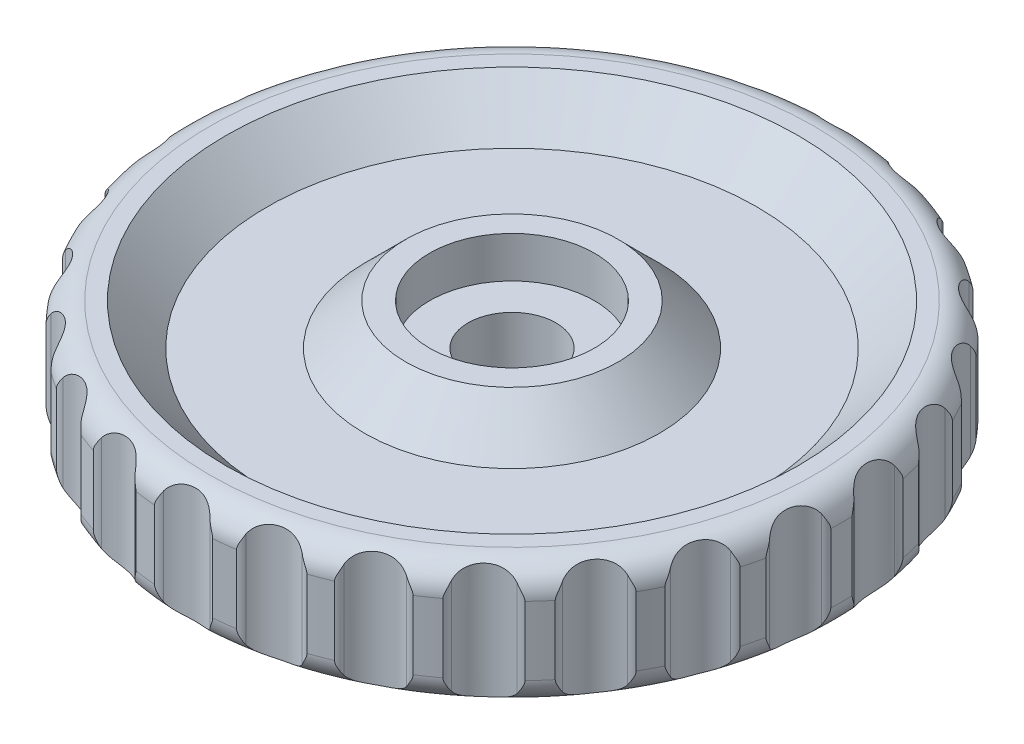
SolidWorks part; units mm, degrees
ref_plane "Front Plane" through (0, 0, 0) normal (0, 0, 1) x (1, 0, 0)
ref_plane "Top Plane" through (0, 0, 0) normal (0, 1, 0) x (1, 0, 0)
ref_plane "Right Plane" through (0, 0, 0) normal (1, 0, 0) x (0, 0, -1)
sketch "Sketch1" plane through (0, 0, 0) normal (0, 1, 0) x (1, 0, 0)
  circle A0 centre (0, 0) radius 1.6
  circle A1 centre (0, 0) radius 12
  dimension "D1" = 24
  dimension "D2" = 3.2
extrude "Boss-Extrude1" add sketch "Sketch1" along normal blind 4.5
fillet "Fillet1" radius 1 2 edges at (0, 0, 12) (0, 4.5, 12)
sketch "Sketch2" plane through (0, 4.5, 0) normal (0, 1, 0) x (1, 0, 0)
  line L0 (0, 14.2529) -> (0, 11.2106) construction
  line L1 (-1.1973, 11.9524) -> (0, 13.275)
  line L2 (0, 13.275) -> (1.1973, 11.9524)
  line L3 (1.6979, 11.8917) -> (3.1769, 12.8893)
  line L4 (3.1769, 12.8893) -> (4.0229, 11.3186)
  line L5 (3.4109, 13.8387) -> (2.6829, 10.8849) construction
  line L6 (4.4944, 11.1398) -> (6.1692, 11.7544)
  line L7 (6.1692, 11.7544) -> (6.6147, 10.0269)
  line L8 (6.6236, 12.6203) -> (5.2098, 9.9265) construction
  line L9 (7.0297, 9.7405) -> (8.803, 9.9365)
  line L10 (8.803, 9.9365) -> (8.8221, 8.1526)
  line L11 (9.4514, 10.6684) -> (7.434, 8.3913) construction
  line L12 (9.1565, 7.7751) -> (10.9251, 7.5411)
  line L13 (10.9251, 7.5411) -> (10.5168, 5.8044)
  line L14 (11.7299, 8.0966) -> (9.2262, 6.3684) construction
  line L15 (10.7512, 5.3579) -> (12.4124, 4.7074)
  line L16 (12.4124, 4.7074) -> (11.6003, 3.1189)
  line L17 (13.3267, 5.0541) -> (10.4821, 3.9753) construction
  line L18 (11.721, 2.6293) -> (13.1782, 1.6001)
  line L19 (13.1782, 1.6001) -> (12.0096, 0.2521)
  line L20 (14.149, 1.718) -> (11.1289, 1.3513) construction
  line L21 (12.0096, -0.2521) -> (13.1782, -1.6001)
  line L22 (13.1782, -1.6001) -> (11.721, -2.6293)
  line L23 (14.149, -1.718) -> (11.1289, -1.3513) construction
  line L24 (11.6003, -3.1189) -> (12.4124, -4.7074)
  line L25 (12.4124, -4.7074) -> (10.7512, -5.3579)
  line L26 (13.3267, -5.0541) -> (10.4821, -3.9753) construction
  line L27 (10.5168, -5.8044) -> (10.9251, -7.5411)
  line L28 (10.9251, -7.5411) -> (9.1565, -7.7751)
  line L29 (11.7299, -8.0966) -> (9.2262, -6.3684) construction
  line L30 (8.8221, -8.1526) -> (8.803, -9.9365)
  line L31 (8.803, -9.9365) -> (7.0297, -9.7405)
  line L32 (9.4514, -10.6684) -> (7.434, -8.3913) construction
  line L33 (6.6147, -10.0269) -> (6.1692, -11.7544)
  line L34 (6.1692, -11.7544) -> (4.4944, -11.1398)
  line L35 (6.6236, -12.6203) -> (5.2098, -9.9265) construction
  line L36 (4.0229, -11.3186) -> (3.1769, -12.8893)
  line L37 (3.1769, -12.8893) -> (1.6979, -11.8917)
  line L38 (3.4109, -13.8387) -> (2.6829, -10.8849) construction
  line L39 (1.1973, -11.9524) -> (0, -13.275)
  line L40 (0, -13.275) -> (-1.1973, -11.9524)
  line L41 (0, -14.2529) -> (0, -11.2106) construction
  line L42 (-1.6979, -11.8917) -> (-3.1769, -12.8893)
  line L43 (-3.1769, -12.8893) -> (-4.0229, -11.3186)
  line L44 (-3.4109, -13.8387) -> (-2.6829, -10.8849) construction
  line L45 (-4.4944, -11.1398) -> (-6.1692, -11.7544)
  line L46 (-6.1692, -11.7544) -> (-6.6147, -10.0269)
  line L47 (-6.6236, -12.6203) -> (-5.2098, -9.9265) construction
  line L48 (-7.0297, -9.7405) -> (-8.803, -9.9365)
  line L49 (-8.803, -9.9365) -> (-8.8221, -8.1526)
  line L50 (-9.4514, -10.6684) -> (-7.434, -8.3913) construction
  line L51 (-9.1565, -7.7751) -> (-10.9251, -7.5411)
  line L52 (-10.9251, -7.5411) -> (-10.5168, -5.8044)
  line L53 (-11.7299, -8.0966) -> (-9.2262, -6.3684) construction
  line L54 (-10.7512, -5.3579) -> (-12.4124, -4.7074)
  line L55 (-12.4124, -4.7074) -> (-11.6003, -3.1189)
  line L56 (-13.3267, -5.0541) -> (-10.4821, -3.9753) construction
  line L57 (-11.721, -2.6293) -> (-13.1782, -1.6001)
  line L58 (-13.1782, -1.6001) -> (-12.0096, -0.2521)
  line L59 (-14.149, -1.718) -> (-11.1289, -1.3513) construction
  line L60 (-12.0096, 0.2521) -> (-13.1782, 1.6001)
  line L61 (-13.1782, 1.6001) -> (-11.721, 2.6293)
  line L62 (-14.149, 1.718) -> (-11.1289, 1.3513) construction
  line L63 (-11.6003, 3.1189) -> (-12.4124, 4.7074)
  line L64 (-12.4124, 4.7074) -> (-10.7512, 5.3579)
  line L65 (-13.3267, 5.0541) -> (-10.4821, 3.9753) construction
  line L66 (-10.5168, 5.8044) -> (-10.9251, 7.5411)
  line L67 (-10.9251, 7.5411) -> (-9.1565, 7.7751)
  line L68 (-11.7299, 8.0966) -> (-9.2262, 6.3684) construction
  line L69 (-8.8221, 8.1526) -> (-8.803, 9.9365)
  line L70 (-8.803, 9.9365) -> (-7.0297, 9.7405)
  line L71 (-9.4514, 10.6684) -> (-7.434, 8.3913) construction
  line L72 (-6.6147, 10.0269) -> (-6.1692, 11.7544)
  line L73 (-6.1692, 11.7544) -> (-4.4944, 11.1398)
  line L74 (-6.6236, 12.6203) -> (-5.2098, 9.9265) construction
  line L75 (-4.0229, 11.3186) -> (-3.1769, 12.8893)
  line L76 (-3.1769, 12.8893) -> (-1.6979, 11.8917)
  line L77 (-3.4109, 13.8387) -> (-2.6829, 10.8849) construction
  arc A0 (-0.847, 11.8378) -> (0.847, 11.8378) centre (0, 12.8028) ccw
  arc A1 (-0.847, 11.8378) -> (-1.1973, 11.9524) centre (-1.1265, 11.5764) ccw
  arc A2 (0.847, 11.8378) -> (1.1973, 11.9524) centre (1.1265, 11.5764) cw
  arc A3 (2.0106, 11.6965) -> (3.6554, 11.2911) centre (3.0639, 12.4308) ccw
  arc A4 (2.0106, 11.6965) -> (1.6979, 11.8917) centre (1.6767, 11.5096) ccw
  arc A5 (3.6554, 11.2911) -> (4.0229, 11.3186) centre (3.8642, 10.9704) cw
  arc A6 (4.7513, 10.8755) -> (6.2513, 10.0882) centre (5.9498, 11.3363) ccw
  arc A7 (4.7513, 10.8755) -> (4.4944, 11.1398) centre (4.3824, 10.7739) ccw
  arc A8 (6.2513, 10.0882) -> (6.6147, 10.0269) centre (6.3773, 9.7269) cw
  arc A9 (7.2159, 9.4224) -> (8.4839, 8.299) centre (8.4898, 9.583) ccw
  arc A10 (7.2159, 9.4224) -> (7.0297, 9.7405) centre (6.8334, 9.412) ccw
  arc A11 (8.4839, 8.299) -> (8.8221, 8.1526) centre (8.5197, 7.9181) cw
  arc A12 (9.2612, 7.4217) -> (10.2235, 6.0276) centre (10.5365, 7.2728) ccw
  arc A13 (9.2612, 7.4217) -> (9.1565, 7.7751) centre (8.8873, 7.5032) ccw
  arc A14 (10.2235, 6.0276) -> (10.5168, 5.8044) centre (10.1671, 5.6491) cw
  arc A15 (10.7682, 4.9897) -> (11.3689, 3.4058) centre (11.9708, 4.5399) ccw
  arc A16 (10.7682, 4.9897) -> (10.7512, 5.3579) centre (10.4247, 5.1583) ccw
  arc A17 (11.3689, 3.4058) -> (11.6003, 3.1189) centre (11.2236, 3.0518) cw
  arc A18 (11.6494, 2.2677) -> (11.8536, 0.5861) centre (12.7094, 1.5432) ccw
  arc A19 (11.6494, 2.2677) -> (11.721, 2.6293) centre (11.3562, 2.5136) ccw
  arc A20 (11.8536, 0.5861) -> (12.0096, 0.2521) centre (11.6278, 0.2771) cw
  arc A21 (11.8536, -0.5861) -> (11.6494, -2.2677) centre (12.7094, -1.5432) ccw
  arc A22 (11.8536, -0.5861) -> (12.0096, -0.2521) centre (11.6278, -0.2771) ccw
  arc A23 (11.6494, -2.2677) -> (11.721, -2.6293) centre (11.3562, -2.5136) cw
  arc A24 (11.3689, -3.4058) -> (10.7682, -4.9897) centre (11.9708, -4.5399) ccw
  arc A25 (11.3689, -3.4058) -> (11.6003, -3.1189) centre (11.2236, -3.0518) ccw
  arc A26 (10.7682, -4.9897) -> (10.7512, -5.3579) centre (10.4247, -5.1583) cw
  arc A27 (10.2235, -6.0276) -> (9.2612, -7.4217) centre (10.5365, -7.2728) ccw
  arc A28 (10.2235, -6.0276) -> (10.5168, -5.8044) centre (10.1671, -5.6491) ccw
  arc A29 (9.2612, -7.4217) -> (9.1565, -7.7751) centre (8.8873, -7.5032) cw
  arc A30 (8.4839, -8.299) -> (7.2159, -9.4224) centre (8.4898, -9.583) ccw
  arc A31 (8.4839, -8.299) -> (8.8221, -8.1526) centre (8.5197, -7.9181) ccw
  arc A32 (7.2159, -9.4224) -> (7.0297, -9.7405) centre (6.8334, -9.412) cw
  arc A33 (6.2513, -10.0882) -> (4.7513, -10.8755) centre (5.9498, -11.3363) ccw
  arc A34 (6.2513, -10.0882) -> (6.6147, -10.0269) centre (6.3773, -9.7269) ccw
  arc A35 (4.7513, -10.8755) -> (4.4944, -11.1398) centre (4.3824, -10.7739) cw
  arc A36 (3.6554, -11.2911) -> (2.0106, -11.6965) centre (3.0639, -12.4308) ccw
  arc A37 (3.6554, -11.2911) -> (4.0229, -11.3186) centre (3.8642, -10.9704) ccw
  arc A38 (2.0106, -11.6965) -> (1.6979, -11.8917) centre (1.6767, -11.5096) cw
  arc A39 (0.847, -11.8378) -> (-0.847, -11.8378) centre (0, -12.8028) ccw
  arc A40 (0.847, -11.8378) -> (1.1973, -11.9524) centre (1.1265, -11.5764) ccw
  arc A41 (-0.847, -11.8378) -> (-1.1973, -11.9524) centre (-1.1265, -11.5764) cw
  arc A42 (-2.0106, -11.6965) -> (-3.6554, -11.2911) centre (-3.0639, -12.4308) ccw
  arc A43 (-2.0106, -11.6965) -> (-1.6979, -11.8917) centre (-1.6767, -11.5096) ccw
  arc A44 (-3.6554, -11.2911) -> (-4.0229, -11.3186) centre (-3.8642, -10.9704) cw
  arc A45 (-4.7513, -10.8755) -> (-6.2513, -10.0882) centre (-5.9498, -11.3363) ccw
  arc A46 (-4.7513, -10.8755) -> (-4.4944, -11.1398) centre (-4.3824, -10.7739) ccw
  arc A47 (-6.2513, -10.0882) -> (-6.6147, -10.0269) centre (-6.3773, -9.7269) cw
  arc A48 (-7.2159, -9.4224) -> (-8.4839, -8.299) centre (-8.4898, -9.583) ccw
  arc A49 (-7.2159, -9.4224) -> (-7.0297, -9.7405) centre (-6.8334, -9.412) ccw
  arc A50 (-8.4839, -8.299) -> (-8.8221, -8.1526) centre (-8.5197, -7.9181) cw
  arc A51 (-9.2612, -7.4217) -> (-10.2235, -6.0276) centre (-10.5365, -7.2728) ccw
  arc A52 (-9.2612, -7.4217) -> (-9.1565, -7.7751) centre (-8.8873, -7.5032) ccw
  arc A53 (-10.2235, -6.0276) -> (-10.5168, -5.8044) centre (-10.1671, -5.6491) cw
  arc A54 (-10.7682, -4.9897) -> (-11.3689, -3.4058) centre (-11.9708, -4.5399) ccw
  arc A55 (-10.7682, -4.9897) -> (-10.7512, -5.3579) centre (-10.4247, -5.1583) ccw
  arc A56 (-11.3689, -3.4058) -> (-11.6003, -3.1189) centre (-11.2236, -3.0518) cw
  arc A57 (-11.6494, -2.2677) -> (-11.8536, -0.5861) centre (-12.7094, -1.5432) ccw
  arc A58 (-11.6494, -2.2677) -> (-11.721, -2.6293) centre (-11.3562, -2.5136) ccw
  arc A59 (-11.8536, -0.5861) -> (-12.0096, -0.2521) centre (-11.6278, -0.2771) cw
  arc A60 (-11.8536, 0.5861) -> (-11.6494, 2.2677) centre (-12.7094, 1.5432) ccw
  arc A61 (-11.8536, 0.5861) -> (-12.0096, 0.2521) centre (-11.6278, 0.2771) ccw
  arc A62 (-11.6494, 2.2677) -> (-11.721, 2.6293) centre (-11.3562, 2.5136) cw
  arc A63 (-11.3689, 3.4058) -> (-10.7682, 4.9897) centre (-11.9708, 4.5399) ccw
  arc A64 (-11.3689, 3.4058) -> (-11.6003, 3.1189) centre (-11.2236, 3.0518) ccw
  arc A65 (-10.7682, 4.9897) -> (-10.7512, 5.3579) centre (-10.4247, 5.1583) cw
  arc A66 (-10.2235, 6.0276) -> (-9.2612, 7.4217) centre (-10.5365, 7.2728) ccw
  arc A67 (-10.2235, 6.0276) -> (-10.5168, 5.8044) centre (-10.1671, 5.6491) ccw
  arc A68 (-9.2612, 7.4217) -> (-9.1565, 7.7751) centre (-8.8873, 7.5032) cw
  arc A69 (-8.4839, 8.299) -> (-7.2159, 9.4224) centre (-8.4898, 9.583) ccw
  arc A70 (-8.4839, 8.299) -> (-8.8221, 8.1526) centre (-8.5197, 7.9181) ccw
  arc A71 (-7.2159, 9.4224) -> (-7.0297, 9.7405) centre (-6.8334, 9.412) cw
  arc A72 (-6.2513, 10.0882) -> (-4.7513, 10.8755) centre (-5.9498, 11.3363) ccw
  arc A73 (-6.2513, 10.0882) -> (-6.6147, 10.0269) centre (-6.3773, 9.7269) ccw
  arc A74 (-4.7513, 10.8755) -> (-4.4944, 11.1398) centre (-4.3824, 10.7739) cw
  arc A75 (-3.6554, 11.2911) -> (-2.0106, 11.6965) centre (-3.0639, 12.4308) ccw
  arc A76 (-3.6554, 11.2911) -> (-4.0229, 11.3186) centre (-3.8642, 10.9704) ccw
  arc A77 (-2.0106, 11.6965) -> (-1.6979, 11.8917) centre (-1.6767, 11.5096) cw
  point P263 (0, 0)
  dimension "D1" = 26
extrude "Cut-Extrude2" cut sketch "Sketch2" against normal through all
sketch "Sketch3" plane through (0, 4.5, 0) normal (0, 1, 0) x (1, 0, 0)
  circle A0 centre (0, 0) radius 8.4142
  circle A1 centre (0, 0) radius 5.8688
  circle A2 centre (0, 0) radius 3
  dimension "D1" = 6
extrude "Cut-Extrude3" cut sketch "Sketch3" against normal blind 1.5 contours A0 A1 | A2 region at (-8.1762, 4.5, 0)
chamfer "Chamfer1" distance 2 angle 45 2 edges at (0, 4.5, 8.4142) (0, 4.5, 5.8688)
sketch "Sketch4" plane through (0, 0, 0) normal (0, -1, 0) x (1, 0, 0)
  line L1 (2.6284, -2.2564) -> (3.2683, 1.148)
  line L2 (3.2683, 1.148) -> (0.6399, 3.4045)
  line L3 (0.6399, 3.4045) -> (-2.6284, 2.2564)
  line L4 (-2.6284, 2.2564) -> (-3.2683, -1.148)
  line L5 (-3.2683, -1.148) -> (-0.6399, -3.4045)
  line L6 (-0.6399, -3.4045) -> (2.6284, -2.2564)
  circle A0 centre (0, 0) radius 3 construction
  dimension "D1" = 6
extrude "Cut-Extrude4" cut sketch "Sketch4" against normal blind 1
